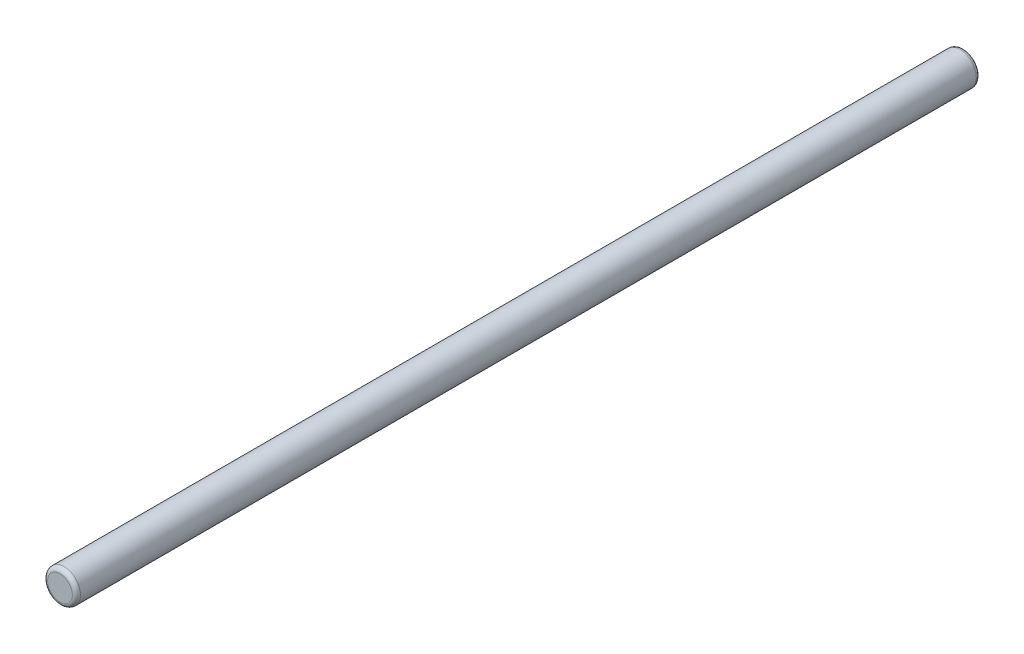
SolidWorks part; units mm, degrees
ref_plane "Ebene vorne" through (0, 0, 0) normal (0, 0, 1) x (1, 0, 0)
ref_plane "Ebene oben" through (0, 0, 0) normal (0, 1, 0) x (1, 0, 0)
ref_plane "Ebene rechts" through (0, 0, 0) normal (1, 0, 0) x (0, 0, -1)
sketch "Skizze1" plane through (0, 0, 0) normal (0, 0, 1) x (1, 0, 0)
  circle A0 centre (0, 0) radius 4
  dimension "D1" = 8
extrude "Aufsatz-Linear austragen1" add sketch "Skizze1" along normal blind 220
fillet "Verrundung1" radius 1 2 edges at (4, 0, 220) (4, 0, 0)
